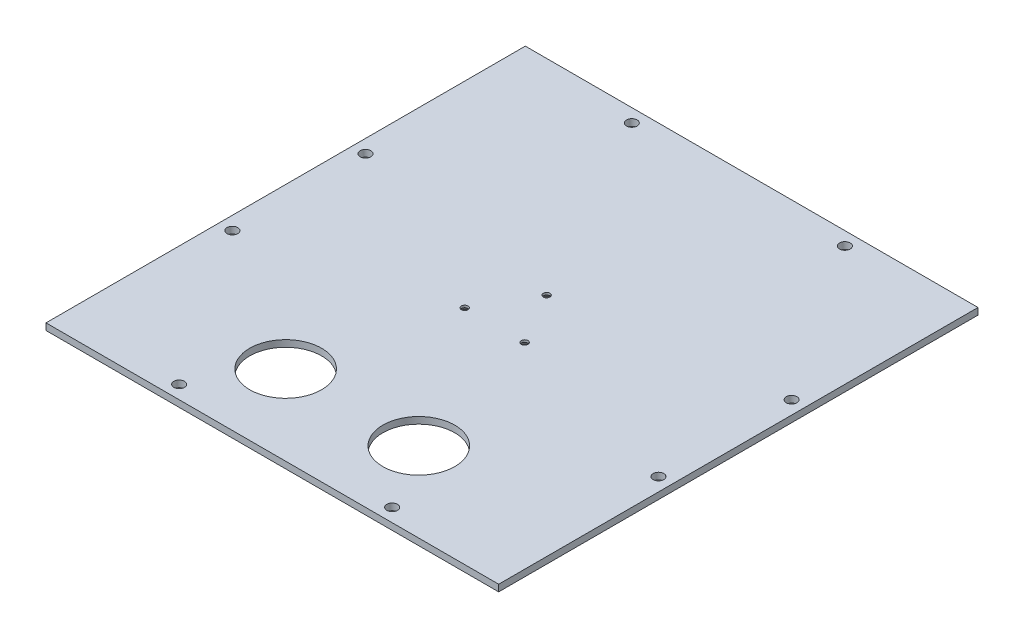
SolidWorks part; units mm, degrees
material "6061-T6 (SS)"
ref_plane "Front Plane" through (0, 0, 0) normal (0, 0, 1) x (1, 0, 0)
ref_plane "Top Plane" through (0, 0, 0) normal (0, 1, 0) x (1, 0, 0)
ref_plane "Right Plane" through (0, 0, 0) normal (1, 0, 0) x (0, 0, -1)
sketch "Sketch1" plane through (0, 0, 0) normal (0, 1, 0) x (1, 0, 0)
  line L1 (0, 0) -> (215.9, 0)
  line L2 (0, 0) -> (0, 228.6)
  line L3 (0, 228.6) -> (215.9, 228.6)
  line L4 (215.9, 0) -> (215.9, 228.6)
  dimension "D1" = 215.9
  dimension "D2" = 228.6
extrude "Boss-Extrude1" add sketch "Sketch1" along normal blind 3.175
sketch "Sketch2" plane through (0, 3.175, 0) normal (0, 1, 0) x (1, 0, 0)
  line L0 (139.7, 38.1) -> (76.2, 38.1) construction
  line L2 (139.7, 38.1) -> (215.9, 38.1) construction
  line L3 (215.9, 0) -> (215.9, 228.6) construction
  line L4 (76.2, 38.1) -> (0, 38.1) construction
  line L5 (0, 0) -> (215.9, 0) construction
  line L6 (0, 228.6) -> (0, 0) construction
  circle A0 centre (139.7, 38.1) radius 17.145
  circle A1 centre (76.2, 38.1) radius 17.145
  point P5 (215.9, 114.3)
  point P13 (107.95, 0)
  point P14 (107.95, 114.3)
  point P15 (-75.9559, 208.7303)
  dimension "D1" = 34.29
  dimension "D2" = 38.1
  dimension "D3" = 63.5
extrude "Cut-Extrude1" cut sketch "Sketch2" against normal through all
sketch "Sketch3" plane through (0, 3.175, 0) normal (0, 1, 0) x (1, 0, 0)
  line L0 (0, 228.6) -> (0, 0) construction
  line L1 (0, 0) -> (215.9, 0) construction
  circle A0 centre (107.95, 130.81) radius 1.5875
  circle A1 centre (122.2481, 106.045) radius 1.5875
  circle A2 centre (93.6519, 106.045) radius 1.5875
  point P0 (0, 114.3)
  point P1 (107.95, 0)
  point P4 (107.95, 114.3)
  dimension "D2" = 3.175
  dimension "D1" = 16.51
  dimension "D3" = 3
extrude "Cut-Extrude2" cut sketch "Sketch3" against normal through all
sketch "Sketch4" plane through (0, 3.175, 0) normal (0, 1, 0) x (1, 0, 0)
  line L0 (215.9, 228.6) -> (0, 228.6) construction
  line L1 (0, 228.6) -> (0, 0) construction
  line L2 (0, 0) -> (215.9, 0) construction
  line L3 (107.95, 228.6) -> (107.95, 0) construction
  circle A0 centre (6.35, 146.05) radius 2.54
  circle A1 centre (6.35, 82.55) radius 2.54
  circle A2 centre (57.15, 6.35) radius 2.54
  circle A3 centre (57.15, 222.25) radius 2.54
  circle A4 centre (158.75, 6.35) radius 2.54
  circle A5 centre (209.55, 82.55) radius 2.54
  circle A6 centre (209.55, 146.05) radius 2.54
  circle A7 centre (158.75, 222.25) radius 2.54
  point P14 (107.95, 0)
  point P15 (107.95, 228.6)
  dimension "D1" = 5.08
  dimension "D2" = 6.35
  dimension "D3" = 6.35
  dimension "D4" = 6.35
  dimension "D5" = 6.35
  dimension "D6" = 57.15
  dimension "D7" = 57.15
  dimension "D8" = 82.55
  dimension "D9" = 82.55
extrude "Cut-Extrude3" cut sketch "Sketch4" against normal through all
chamfer "Chamfer1" distance 2.1082 angle 41 3 edges at (93.6519, 0, -104.4575) (122.2481, 0, -104.4575) (107.95, 0, -129.2225) first distance on face at (93.6519, 0, -104.4575) first distance on face at (122.2481, 0, -104.4575) first distance on face at (107.95, 0, -129.2225)
sketch "Sketch5" plane through (0, 0, 0) normal (0, -1, 0) x (1, 0, 0)
  line L0 (215.9, -228.6) -> (0, -228.6) construction
  line L1 (95.25, -120.65) -> (19.05, -120.65)
  line L2 (95.25, -120.65) -> (95.25, -209.55)
  line L3 (95.25, -209.55) -> (19.05, -209.55)
  line L4 (19.05, -120.65) -> (19.05, -209.55)
  line L5 (0, -228.6) -> (0, 0) construction
  line L6 (107.95, -130.81) -> (107.95, -50130.81) construction
  line L7 (19.05, -95.25) -> (95.25, -95.25)
  line L9 (19.05, -69.85) -> (95.25, -69.85)
  line L10 (95.25, -95.25) -> (95.25, -69.85)
  line L11 (0, 0) -> (215.9, 0) construction
  line L13 (19.05, -95.25) -> (19.05, -19.05)
  line L14 (19.05, -19.05) -> (44.45, -19.05)
  line L15 (44.45, -95.25) -> (44.45, -19.05)
  line L16 (120.65, -209.55) -> (196.85, -209.55)
  line L17 (196.85, -120.65) -> (196.85, -209.55)
  line L18 (120.65, -120.65) -> (196.85, -120.65)
  line L19 (120.65, -120.65) -> (120.65, -209.55)
  line L20 (196.85, -69.85) -> (120.65, -69.85)
  line L21 (120.65, -95.25) -> (120.65, -69.85)
  line L22 (196.85, -95.25) -> (120.65, -95.25)
  line L24 (196.85, -19.05) -> (171.45, -19.05)
  line L25 (171.45, -95.25) -> (171.45, -19.05)
  line L27 (196.85, -95.25) -> (196.85, -19.05)
  circle A0 centre (76.2, -38.1) radius 17.145 construction
  point P8 (0, -114.3)
  dimension "D1" = 19.05
  dimension "D2" = 19.05
  dimension "D3" = 6.35
  dimension "D4" = 76.2
  dimension "D5" = 19.05
  dimension "D6" = 31.75
  dimension "D7" = 19.05
  dimension "D8" = 31.75
extrude "Cut-Extrude4" cut sketch "Sketch5" against normal blind 1.5875 contours L9 L15 L14 L13 | L7 L15 L9 L13 | L15 L7 L10 L9 | L1 L4 L3 L2 | L18 L19 L16 L17 | L22 L25 L20 L21 | L22 L27 L20 L25 | L20 L27 L24 L25 region at (57.15, 0, -165.1) region at (31.75, 0, -82.55) region at (69.85, 0, -82.55) region at (31.75, 0, -44.45) region at (158.75, 0, -165.1) region at (184.15, 0, -82.55) region at (184.15, 0, -44.45) region at (146.05, 0, -82.55)
fillet "Fillet1" radius 3.175 18 edges at (19.05, 0.7937, -95.25) (95.25, 0.7937, -95.25) (95.25, 0.7937, -69.85) (44.45, 0.7937, -19.05) (19.05, 0.7937, -19.05) (196.85, 0.7937, -19.05) (196.85, 0.7937, -95.25) (171.45, 0.7937, -19.05) (120.65, 0.7937, -69.85) (120.65, 0.7937, -95.25) (196.85, 0.7937, -120.65) (120.65, 0.7937, -120.65) (120.65, 0.7937, -209.55) (196.85, 0.7937, -209.55) (95.25, 0.7937, -209.55) (95.25, 0.7937, -120.65) (19.05, 0.7937, -209.55) (19.05, 0.7937, -120.65)
fillet "Fillet2" radius 25.4 2 edges at (171.45, 0.7937, -69.85) (44.45, 0.7937, -69.85)
